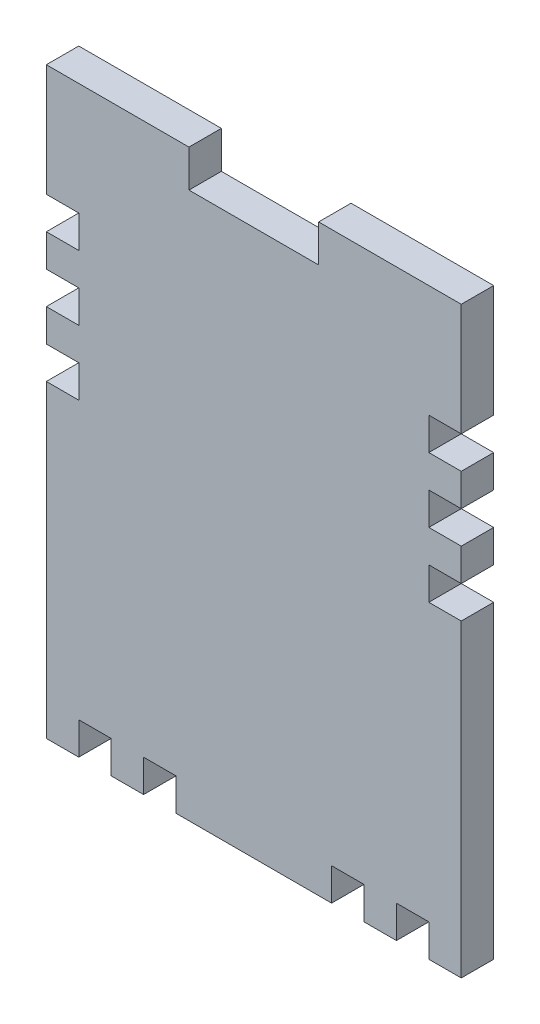
SolidWorks part; units mm, degrees
ref_plane "Plan de face" through (0, 0, 0) normal (0, 0, 1) x (1, 0, 0)
ref_plane "Plan de dessus" through (0, 0, 0) normal (0, 1, 0) x (1, 0, 0)
ref_plane "Plan de droite" through (0, 0, 0) normal (1, 0, 0) x (0, 0, -1)
sketch "Esquisse2" plane through (0, 0, 0) normal (0, 0, 1) x (1, 0, 0)
  line L97 (62.436, 160.0452) -> (62.436, 76.8543) construction
  line L98 (62.436, 76.8543) -> (62.436, 160.0452) construction
  line L99 (72.436, 161.1087) -> (52.436, 161.1087)
  line L100 (52.436, 161.1087) -> (52.436, 166.8543)
  line L101 (52.436, 166.8543) -> (30.436, 166.8543)
  line L102 (30.436, 166.8543) -> (30.436, 149.5443)
  line L103 (30.436, 149.5443) -> (35.436, 149.5443)
  line L104 (35.436, 149.5443) -> (35.436, 144.5443)
  line L105 (35.436, 144.5443) -> (30.436, 144.5443)
  line L106 (30.436, 144.5443) -> (30.436, 139.5443)
  line L107 (30.436, 139.5443) -> (35.436, 139.5443)
  line L108 (35.436, 139.5443) -> (35.436, 134.5443)
  line L109 (35.436, 134.5443) -> (30.436, 134.5443)
  line L110 (30.436, 134.5443) -> (30.436, 129.5443)
  line L111 (30.436, 129.5443) -> (35.436, 129.5443)
  line L112 (35.436, 129.5443) -> (35.436, 124.5443)
  line L113 (35.436, 124.5443) -> (30.436, 124.5443)
  line L114 (30.436, 124.5443) -> (30.436, 76.8543)
  line L115 (30.436, 76.8543) -> (35.436, 76.8543)
  line L116 (35.436, 76.8543) -> (35.436, 81.8543)
  line L117 (35.436, 81.8543) -> (40.436, 81.8543)
  line L118 (40.436, 81.8543) -> (40.436, 76.8543)
  line L119 (40.436, 76.8543) -> (45.436, 76.8543)
  line L120 (45.436, 76.8543) -> (45.436, 81.8543)
  line L121 (45.436, 81.8543) -> (50.436, 81.8543)
  line L122 (50.436, 81.8543) -> (50.436, 76.8543)
  line L123 (50.436, 76.8543) -> (74.436, 76.8543)
  line L125 (74.436, 81.8543) -> (74.436, 76.8543)
  line L126 (79.436, 81.8543) -> (74.436, 81.8543)
  line L127 (79.436, 76.8543) -> (79.436, 81.8543)
  line L128 (84.436, 76.8543) -> (79.436, 76.8543)
  line L129 (84.436, 81.8543) -> (84.436, 76.8543)
  line L130 (89.436, 81.8543) -> (84.436, 81.8543)
  line L131 (89.436, 76.8543) -> (89.436, 81.8543)
  line L132 (94.436, 76.8543) -> (89.436, 76.8543)
  line L133 (94.436, 124.5443) -> (94.436, 76.8543)
  line L134 (89.436, 124.5443) -> (94.436, 124.5443)
  line L135 (89.436, 129.5443) -> (89.436, 124.5443)
  line L136 (94.436, 129.5443) -> (89.436, 129.5443)
  line L137 (94.436, 134.5443) -> (94.436, 129.5443)
  line L138 (89.436, 134.5443) -> (94.436, 134.5443)
  line L139 (89.436, 139.5443) -> (89.436, 134.5443)
  line L140 (94.436, 139.5443) -> (89.436, 139.5443)
  line L141 (94.436, 144.5443) -> (94.436, 139.5443)
  line L142 (89.436, 144.5443) -> (94.436, 144.5443)
  line L143 (89.436, 149.5443) -> (89.436, 144.5443)
  line L144 (94.436, 149.5443) -> (89.436, 149.5443)
  line L145 (94.436, 166.8543) -> (94.436, 149.5443)
  line L146 (72.436, 166.8543) -> (94.436, 166.8543)
  line L147 (72.436, 161.1087) -> (72.436, 166.8543)
  point P50 (62.436, 161.1087)
  dimension "D3" = 5
  dimension "D1" = 90
  dimension "D2" = 17.31
  dimension "D4" = 5
  dimension "D5" = 5
  dimension "D6" = 5
  dimension "D7" = 32
  dimension "D8" = 10
extrude "Boss.-Extru.1" add sketch "Esquisse2" along normal blind 5 contours L128 L111 L110 L108 L107 L106 L105 L104 L102 L146 L145 | L120 L141 L140 L139 L138 L137 L136 L135 L134 L133 L132 L131 L130 L113 L114 L117 region at (62.436, 121.3225, 0)
